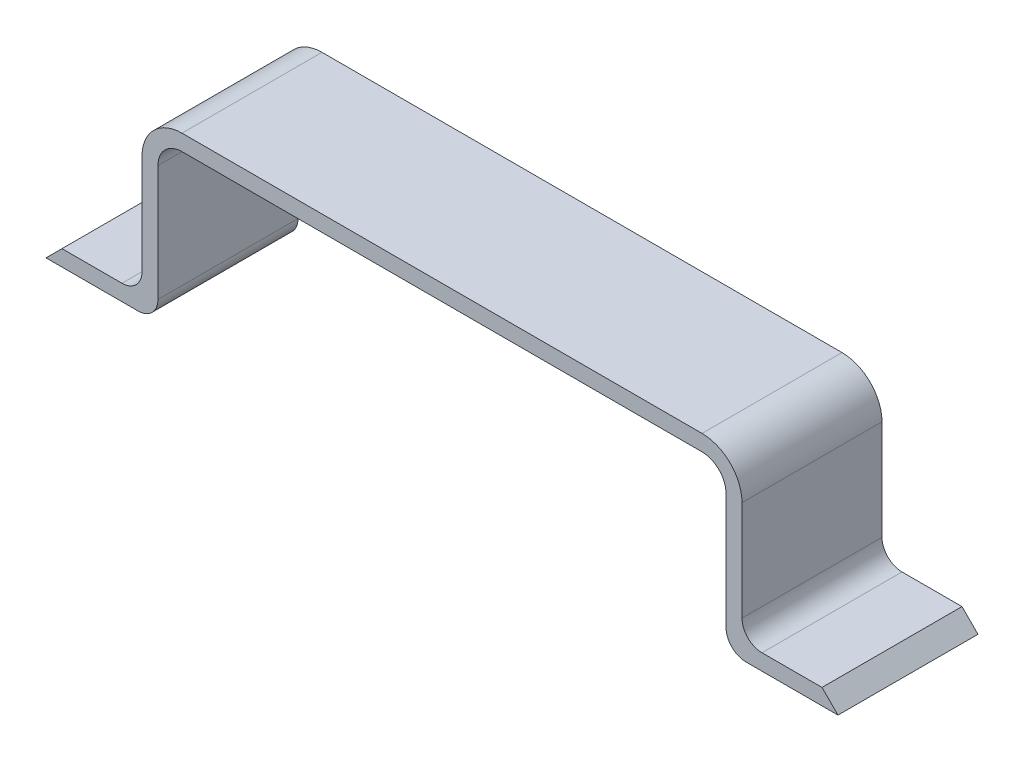
SolidWorks part; units mm, degrees
ref_plane "Front Plane" through (0, 0, 0) normal (0, 0, 1) x (1, 0, 0)
ref_plane "Top Plane" through (0, 0, 0) normal (0, 1, 0) x (1, 0, 0)
ref_plane "Right Plane" through (0, 0, 0) normal (1, 0, 0) x (0, 0, -1)
sketch "Sketch1" plane through (0, 0, 0) normal (0, 0, 1) x (1, 0, 0)
  line L0 (-100, 0) -> (-80, 0)
  line L1 (-75, 5) -> (-75, 30)
  line L2 (-65, 40) -> (65, 40)
  line L3 (75, 30) -> (75, 5)
  line L4 (80, 0) -> (100, 0)
  line L5 (-100, -4) -> (-76, -4)
  line L6 (-71, 1) -> (-71, 30)
  line L7 (-65, 36) -> (65, 36)
  line L8 (71, 30) -> (71, 1)
  line L9 (76, -4) -> (100, -4)
  line L10 (71, 30) -> (71, -4) construction
  line L11 (71, -4) -> (100, -4) construction
  line L12 (75, 30) -> (75, 0) construction
  line L13 (75, 0) -> (100, 0) construction
  line L14 (-100, -4) -> (-71, -4) construction
  line L15 (-71, -4) -> (-71, 30) construction
  line L16 (-100, 0) -> (-75, 0) construction
  line L17 (-75, 0) -> (-75, 30) construction
  line L18 (-100, 0) -> (-100, -4)
  line L19 (100, 0) -> (100, -4)
  arc A0 (65, 40) -> (75, 30) centre (65, 30) cw
  arc A1 (-75, 30) -> (-65, 40) centre (-65, 30) cw
  arc A2 (-71, 30) -> (-65, 36) centre (-65, 30) cw
  arc A3 (65, 36) -> (71, 30) centre (65, 30) cw
  arc A4 (71, 1) -> (76, -4) centre (76, 1) ccw
  arc A5 (75, 5) -> (80, 0) centre (80, 5) ccw
  arc A6 (-76, -4) -> (-71, 1) centre (-76, 1) ccw
  arc A7 (-80, 0) -> (-75, 5) centre (-80, 5) ccw
  point P11 (-75, 40)
  point P28 (75, 0)
  point P35 (-75, 0)
  dimension "D6" = 10
  dimension "D8" = 5
  dimension "D1" = 200
  dimension "D2" = 25
  dimension "D3" = 25
  dimension "D4" = 100
  dimension "D5" = 40
  dimension "D7" = 4
extrude "Boss-Extrude1" add sketch "Sketch1" along normal mid plane 35
chamfer "Chamfer1" distance 5 angle 45 2 edges at (-100, 0, 0) (100, 0, 0)
